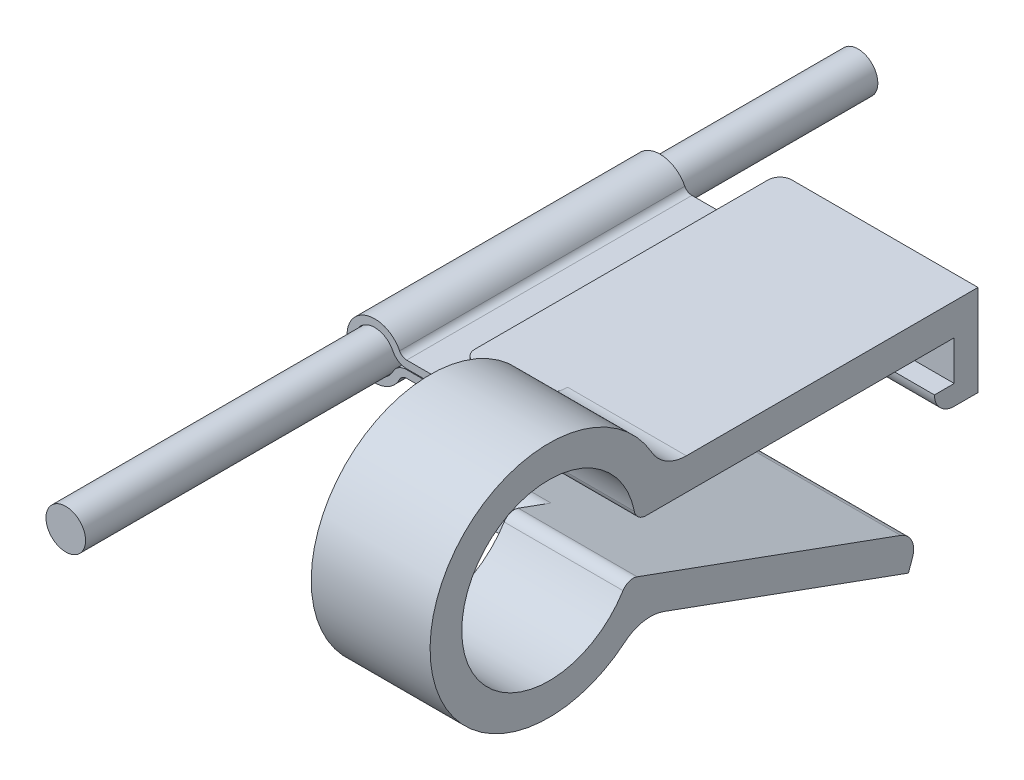
SolidWorks part; units mm, degrees
ref_plane "Front Plane" through (0, 0, 0) normal (0, 0, 1) x (1, 0, 0)
ref_plane "Top Plane" through (0, 0, 0) normal (0, 1, 0) x (1, 0, 0)
ref_plane "Right Plane" through (0, 0, 0) normal (1, 0, 0) x (0, 0, -1)
sketch "Sketch1" plane through (0, 0, 0) normal (0, 0, 1) x (1, 0, 0)
  circle A0 centre (0, 0) radius 0.5
  dimension "D1" = 1
extrude "Boss-Extrude1" add sketch "Sketch1" along normal blind 20
ref_plane "Plane1" through (0, 0, 5) normal (0, 0, -1) x (-1, 0, 0)
sketch "Sketch3" plane through (0, 0, 5) normal (0, 0, -1) x (-1, 0, 0)
  line L0 (0, 0) -> (-5.5026, 0) construction
  line L1 (-0.8062, -0.2) -> (-4.2285, -0.2)
  line L2 (-4.2285, 0.2) -> (-0.8062, 0.2)
  circle A0 centre (0, 0) radius 0.5 construction
  arc A2 (-0.6271, 0.3111) -> (-0.6271, -0.3111) centre (0, 0) cw
  arc A3 (-0.6271, -0.3111) -> (-0.8062, -0.2) centre (-0.8062, -0.4) ccw
  arc A4 (-0.6271, 0.3111) -> (-0.8062, 0.2) centre (-0.8062, 0.4) cw
  dimension "D1" = 0.2
  dimension "D4" = 0.2
  dimension "D2" = 0.2
  dimension "D3" = 0.2
extrude "Extrude-Thin1" add sketch "Sketch3" against normal blind 7.2 separate body thin contours L2 A4 A2 A3 L1 thin type one direction wall 0.19
sketch "Sketch4" plane through (0, 0.2, 0) normal (0, 1, 0) x (1, 0, 0)
  line L0 (0.8062, -12.2) -> (0.8062, -5) construction
  line L1 (0.8062, -13.2) -> (5.8062, -13.2)
  line L2 (0.8062, -13.2) -> (0.8062, -4)
  line L3 (0.8062, -4) -> (5.8062, -4)
  line L4 (5.8062, -13.2) -> (5.8062, -4)
  line L5 (4.2285, -12.2) -> (0.8062, -12.2) construction
  line L6 (4.2285, -5) -> (0.8062, -5) construction
  line L7 (0.8062, -12.4) -> (5.8062, -12.4)
  line L8 (0.8062, -4.8) -> (5.8062, -4.8)
  dimension "D1" = 5
  dimension "D2" = 1
  dimension "D3" = 1
  dimension "D4" = 0.8
  dimension "D5" = 0.8
sketch "Sketch5" plane through (4.2285, 0, 0) normal (1, 0, 0) x (0, 0, -1)
  line L0 (-4.8, -0.8) -> (-5.3, -0.8)
  line L1 (-12.2, 0.2) -> (-4.2, 0.2)
  line L2 (-12.2, 0.2) -> (-12.2, 1)
  line L3 (-12.2, 1) -> (-4.2, 1)
  line L4 (-4.2, 0.2) -> (-4.2, 1)
  line L5 (-4.2, 1) -> (-4.832, 1)
  line L6 (-4.2, 1) -> (-4.2, -1.3)
  line L7 (-4.2, -1.3) -> (-4.8, -1.3)
  line L8 (-4.8, -0.8) -> (-4.8, -1.3)
  line L9 (-4.8, -0.8) -> (-4.8, 0.2)
  line L10 (-5, 0.01) -> (-5, 0.2) construction
  line L11 (-12.2, 0.2) -> (-12.8402, 0.2)
  line L12 (-15.0319, 0.01) -> (-12.2, 0.01) construction
  line L13 (-5, -0.55) -> (-5, 0.55) construction
  line L14 (-12.2, -0.2) -> (-5, -0.2)
  line L15 (-12.2, -0.2) -> (-12.2, -0.8)
  line L16 (-12.2, -0.8) -> (-5, -0.8)
  line L17 (-5, -0.2) -> (-5, -0.8)
  line L18 (-12.4493, -1.1535) -> (-5.6835, -3.616)
  line L19 (-12.4493, -1.1535) -> (-12.7229, -1.9053)
  line L20 (-5.6835, -3.616) -> (-5.9571, -4.3678)
  line L21 (-12.7229, -1.9053) -> (-5.9571, -4.3678)
  line L22 (-15.0319, 0.01) -> (-5.0092, -3.638) construction
  line L23 (-12.2, 0.01) -> (-12.2, -0.2) construction
  line L24 (-12.4493, -1.1535) -> (-12.3774, -0.9562) construction
  line L25 (-12.4493, -1.1535) -> (-13.0459, -0.9363)
  arc A0 (-4.8, -1.3) -> (-5.3, -0.8) centre (-4.8, -0.8) cw
  circle A1 centre (-15.0319, 0.01) radius 3
  circle A2 centre (-15.0319, 0.01) radius 2.2
  line M13 (-5, 0.2) -> (-12.2, 0.2)
  dimension "D1" = 0.6
  dimension "D6" = 0.8
  dimension "D8" = 6
  dimension "D2" = 0.5
  dimension "D3" = 0.8
  dimension "D4" = 0.6
  dimension "D5" = 0.2
  dimension "D7" = 0.8
  dimension "D9" = 20
extrude "Boss-Extrude2" add sketch "Sketch5" along normal blind 3 separate body contours A2 L11 L2 A1 L19 L25 | A1 L1 L4 L3 M13 | L1 A1 L2 | A1 L21 L20 L18 | L19 A1 L18 | L9 L8 L7 L6 L1 | A0 L8 L0 region at (4.2285, -1.0122, 5.0122) region at (4.2285, -0.55, 4.5) region at (4.2285, 0.6014, 8.1501) region at (4.2285, 0.4924, 12.1388) region at (4.2285, -1.4493, 12.4897) region at (4.2285, -2.7797, 9.1555) region at (4.2285, 0.2837, 12.5201)
extrude "Boss-Extrude3" add sketch "Sketch5<3>" against normal blind 2 contours A1 L1 L4 L3 M13 | A1 L21 L20 L18 | L1 A1 L2 | L19 A1 L18 region at (4.2285, 0.6014, 8.1501) region at (4.2285, 0.4924, 12.1388) region at (4.2285, -1.4493, 12.4897) region at (4.2285, -2.7797, 9.1555)
sketch "Sketch5<3>" plane through (4.2285, 0, 0) normal (1, 0, 0) x (0, 0, -1) same geometry as "Sketch5"
fillet "Fillet2" radius 0.5 4 edges at (4.7285, -3.616, 5.6835) (3.2285, -1.1535, 12.4493)
fillet "Fillet3" radius 1 2 edges at (5.7285, 1, 12.2) (5.7285, -1.9053, 12.7229)
fillet "Fillet4" radius 0.3 10 edges at (2.2285, 0.85, 4.2) (2.2285, 0.3464, 4.3464) (2.2285, 0.85, 12.2) (2.2285, 0.3464, 12.0536) (2.2285, -1.7643, 12.6716) (2.2285, -1.3412, 12.3617) (2.2285, -4.2268, 5.9058) (2.2285, -3.7036, 5.8712) (2.2285, 0.2, 8.2) (2.2285, -2.3848, 9.0664)
fillet "Fillet5" radius 0.3 2 edges at (5.7285, -0.9363, 13.0459) (5.7285, 0.2, 12.8402)
